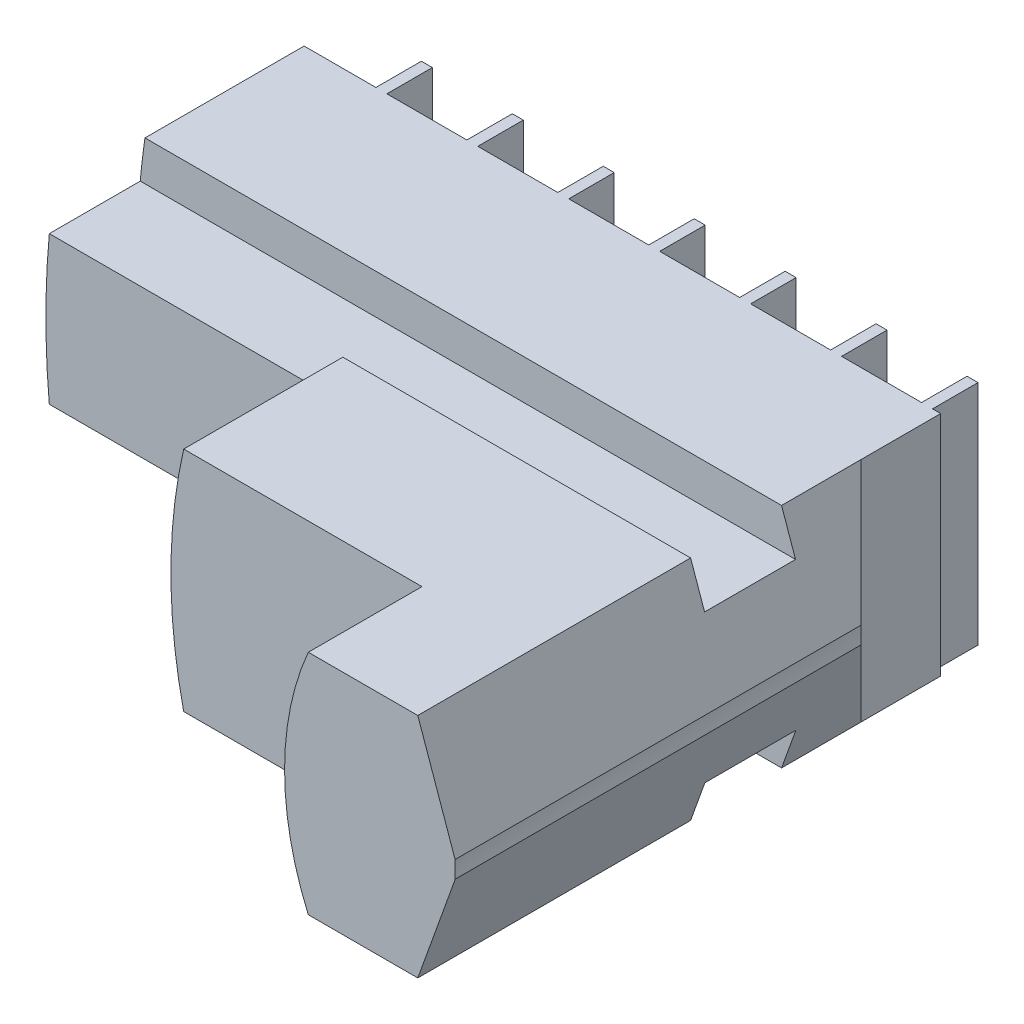
SolidWorks part; units mm, degrees
ref_plane "Front Plane" through (0, 0, 0) normal (0, 0, 1) x (1, 0, 0)
ref_plane "Top Plane" through (0, 0, 0) normal (0, 1, 0) x (1, 0, 0)
ref_plane "Right Plane" through (0, 0, 0) normal (1, 0, 0) x (0, 0, -1)
sketch "Sketch1" plane through (0, 0, 0) normal (0, 0, 1) x (1, 0, 0)
  line L0 (-13.282, -10) -> (-9.9878, -0.8272)
  line L1 (-69.282, -10) -> (-13.282, -10)
  line L2 (-69.282, 10) -> (-13.282, 10)
  line L3 (-13.282, 10) -> (-10, 0.6644)
  arc A0 (-69.282, 10) -> (-69.282, -10) centre (0, 0) ccw
  arc A1 (-43.8748, 10) -> (-43.8748, -10) centre (0, 0) ccw
  arc A2 (-22.9129, 10) -> (-22.9129, -10) centre (0, 0) ccw
  arc A3 (-10, 0.6644) -> (-9.9878, -0.8272) centre (0, 0) ccw
  dimension "D2" = 56
  dimension "D3" = 56
  dimension "D4" = 10
extrude "Boss-Extrude1" add sketch "Sketch1" along normal blind 22 contours A1 L2 A0 L1 region at (-57.1927, 0, 0)
extrude "Boss-Extrude2" add sketch "Sketch1<3>" along normal blind 36 contours A2 L2 A1 L1 region at (-34.4649, 0, 0)
sketch "Sketch1<3>" plane through (0, 0, 0) normal (0, 0, 1) x (1, 0, 0) same geometry as "Sketch1"
extrude "Boss-Extrude3" add sketch "Sketch1<4>" along normal blind 46 contours A3 L3 L2 A2 L1 L0 region at (-17.8918, -0.0048, 0)
sketch "Sketch1<4>" plane through (0, 0, 0) normal (0, 0, 1) x (1, 0, 0) same geometry as "Sketch1"
ref_plane "Plane1" through (-70, 0, 0) normal (-1, 0, 0) x (0, 0, 1)
sketch "Sketch4" plane through (-70, 0, 0) normal (-1, 0, 0) x (0, 0, 1)
  line L0 (-1000, 0) -> (49000, 0) construction
  line L2 (22, -10) -> (22, 10) construction
  line L3 (22, 6.5) -> (14, 6.5)
  line L4 (14, 6.5) -> (14, 10)
  line L6 (22, 6.5) -> (22, 10)
  line L7 (22, -6.5) -> (22, -10)
  line L8 (14, -6.5) -> (14, -10)
  line L9 (22, -6.5) -> (14, -6.5)
  line L10 (14, 10) -> (22, 10)
  line L11 (14, -10) -> (22, -10)
  dimension "D1" = 8
  dimension "D2" = 13
extrude "Cut-Extrude1" cut sketch "Sketch4" against normal through all
sketch "Sketch7" plane through (0, 0, 0) normal (0, 0, -1) x (-1, 0, 0)
  line L1 (14, -10) -> (14, 10)
  line L2 (69.282, -10) -> (13.282, -10) construction
  line L3 (69.282, 10) -> (13.282, 10) construction
  line L4 (69.282, -10) -> (14, -10)
  line L5 (69.282, 10) -> (14, 10)
  arc A1 (14.9666, -10) -> (14.9666, 10) centre (0, 0) ccw
  line M7 (13.282, -10) -> (69.282, -10)
sketch "Sketch8" plane through (0, 0, 0) normal (0, 1, 0) x (1, 0, 0)
  line L0 (-13.282, -7) -> (-9.9878, -10.2942)
  line L2 (-13.282, -14) -> (-13.282, 0) construction
  line L3 (-9.9878, -46) -> (-9.9878, 0) construction
  line L4 (-13.282, -7) -> (-13.282, 0)
  line L5 (-13.282, 0) -> (-9.9878, 0)
  line L6 (-9.9878, 0) -> (-9.9878, -10.2942)
  dimension "D1" = 45
extrude "Cut-Extrude3" cut sketch "Sketch8" against normal through all both and the other way through all
extrude "Boss-Extrude4" add sketch "Sketch7" along normal blind 4 contours A1 L5 L1 M7 region at (-15.6442, 0, 0)
pattern_linear "LPattern1" count 7 spacing 8 along (-1, 0, 0) of "Boss-Extrude4"
